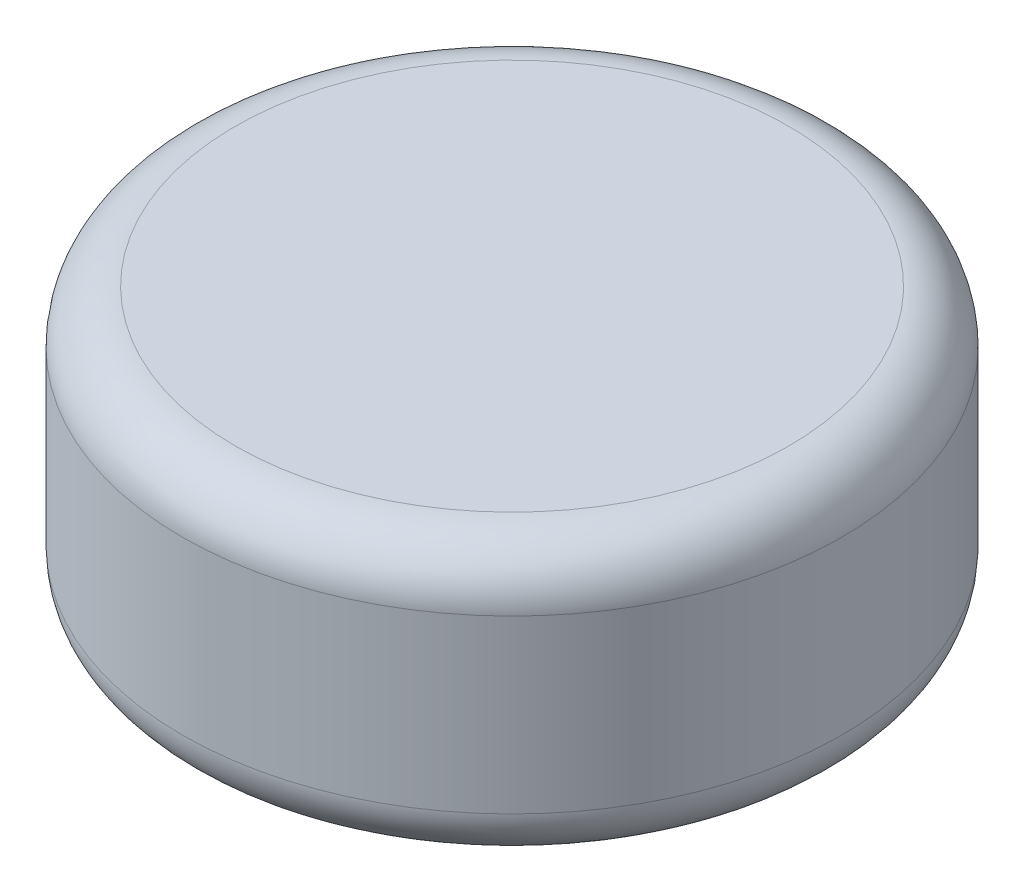
SolidWorks part; units mm, degrees
ref_plane "Front Plane" through (0, 0, 0) normal (0, 0, 1) x (1, 0, 0)
ref_plane "Top Plane" through (0, 0, 0) normal (0, 1, 0) x (1, 0, 0)
ref_plane "Right Plane" through (0, 0, 0) normal (1, 0, 0) x (0, 0, -1)
sketch "Sketch1" plane through (0, 0, 0) normal (0, 1, 0) x (1, 0, 0)
  line L1 (-3.3655, -3.3655) -> (3.3655, -3.3655)
  line L2 (-3.3655, -3.3655) -> (-3.3655, 3.3655)
  line L3 (-3.3655, 3.3655) -> (3.3655, 3.3655)
  line L4 (3.3655, -3.3655) -> (3.3655, 3.3655)
  line L5 (-3.3655, -3.3655) -> (3.3655, 3.3655) construction
  line L6 (-3.3655, 3.3655) -> (3.3655, -3.3655) construction
  circle A0 centre (0, 0) radius 9.525
  circle A1 centre (0, 0) radius 3.3414 construction
  dimension "D1" = 19.05
  dimension "D2" = 6.731
  dimension "D3" = 6.731
extrude "Boss-Extrude1" add sketch "Sketch1" along normal mid plane 8.001 contours L1 L4 L3 L2 | A0 L4 L1 L2 L3 region at (0, 0, 0) region at (-9.2556, 0, 0)
extrude "Cut-Extrude1" cut sketch "Sketch1<3>" against normal mid plane 6.731 contours L1 L4 L3 L2 region at (0, 0, 0)
sketch "Sketch1<3>" plane through (0, 0, 0) normal (0, 1, 0) x (1, 0, 0) same geometry as "Sketch1"
fillet "Fillet1" radius 1.524 2 edges at (0, 4.0005, 9.525) (0, -4.0005, 9.525)
equation "\"SQR.MAGNET.L\"=0.265"
equation "\"D2@Sketch1\"=\"SQR.MAGNET.L\""
equation "\"D3@Sketch1\"=\"SQR.MAGNET.L\""
